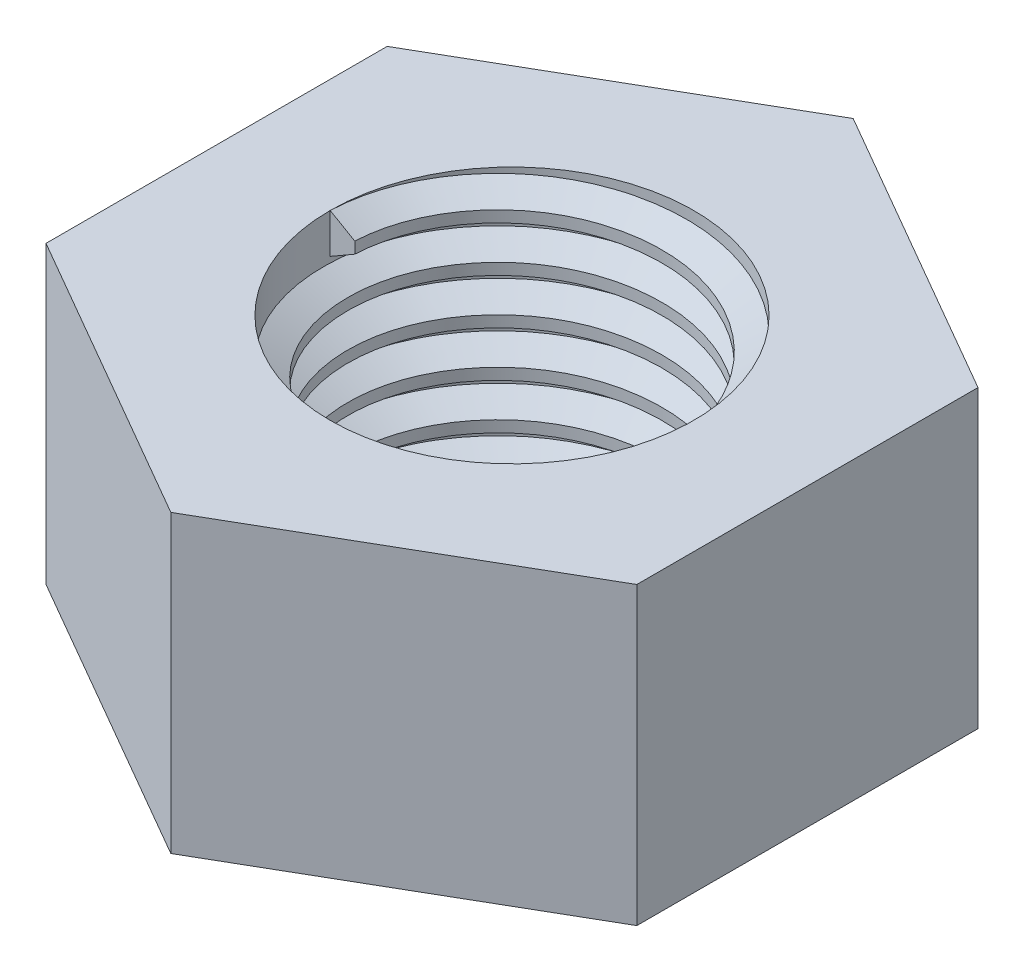
SolidWorks part; units mm, degrees
ref_plane "Ebene vorne" through (0, 0, 0) normal (0, 0, 1) x (1, 0, 0)
ref_plane "Ebene oben" through (0, 0, 0) normal (0, 1, 0) x (1, 0, 0)
ref_plane "Ebene rechts" through (0, 0, 0) normal (1, 0, 0) x (0, 0, -1)
sketch "Skizze1" plane through (0, 0, 0) normal (0, 1, 0) x (1, 0, 0)
  line L1 (6.4998, -3.7531) -> (6.5002, 3.7524)
  line L2 (6.5002, 3.7524) -> (0.0004, 7.5056)
  line L3 (0.0004, 7.5056) -> (-6.4998, 3.7531)
  line L4 (-6.4998, 3.7531) -> (-6.5002, -3.7524)
  line L5 (-6.5002, -3.7524) -> (-0.0004, -7.5056)
  line L6 (-0.0004, -7.5056) -> (6.4998, -3.7531)
  circle A0 centre (0, 0) radius 6.5 construction
  dimension "D1" = 13
extrude "Aufsatz-Linear austragen1" add sketch "Skizze1" against normal blind 6.5
sketch "Skizze2" plane through (0, 0, 0) normal (0, 1, 0) x (1, 0, 0)
  circle A0 centre (0, 0) radius 4
  dimension "D1" = 8
extrude "Schnitt-Linear austragen1" cut sketch "Skizze2" against normal blind 6.5
thread "Gewinde1" pitch 1 method extrude profile "Gewindeprofil3" start angle 0, offset 0, length 0, pitch 1, diameter 8
ref_plane "Ebene3" through (-4, 0, 0) normal (0, 0, 1) x (-1, 0, 0)
sketch "Gewindeprofil3" plane through (-4, 0, 0) normal (0, 0, 1) x (-1, 0, 0)
  line L0 (0, 0) -> (0, 1) construction
  line L11 (0, 0) -> (0, 0.875)
  line L12 (0, 0.875) -> (-0.5413, 0.5625)
  line L13 (-0.5413, 0.5625) -> (-0.5413, 0.3125)
  line L15 (-0.5413, 0.3125) -> (0, 0)
  line L17 (-0.5413, 0.4375) -> (0, 0.4375) construction
  point P2 (0, 0)
  dimension "Pitch" = 1
  dimension "Profile_Angle" = 60
  dimension "Profile_Land" = 0.25
  dimension "Profile_Height" = 0.5413
